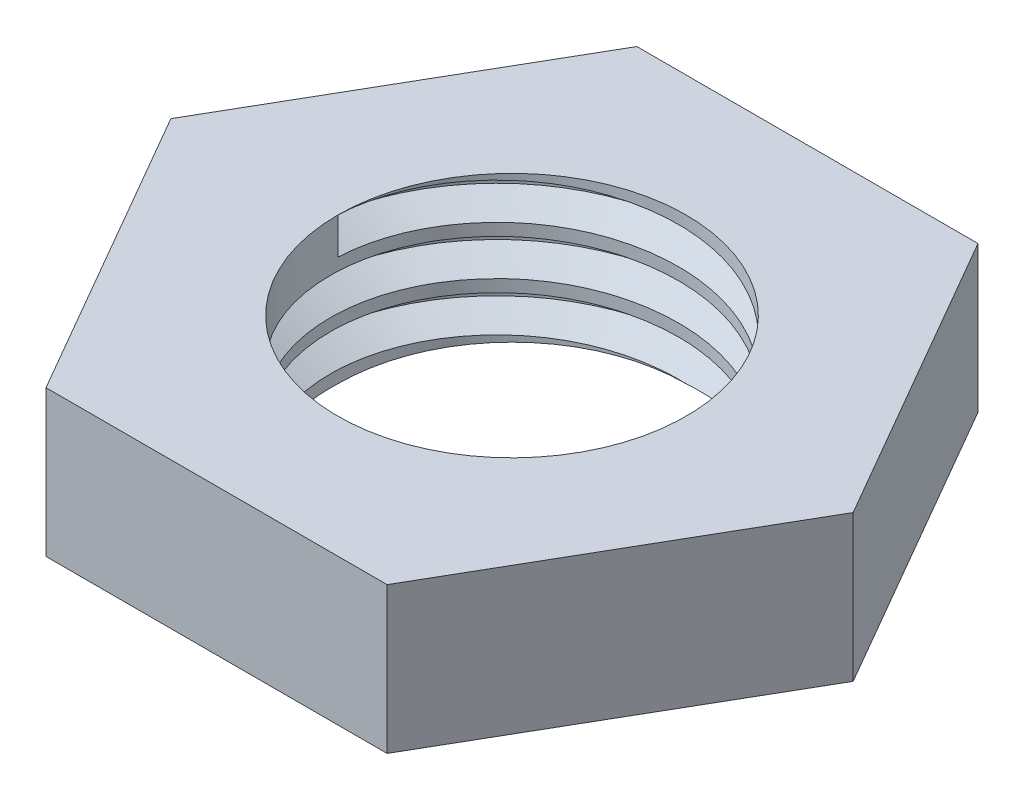
SolidWorks part; units mm, degrees
ref_plane "Front Plane" through (0, 0, 0) normal (0, 0, 1) x (1, 0, 0)
ref_plane "Top Plane" through (0, 0, 0) normal (0, 1, 0) x (1, 0, 0)
ref_plane "Right Plane" through (0, 0, 0) normal (1, 0, 0) x (0, 0, -1)
sketch "Sketch1" plane through (0, 0, 0) normal (0, 1, 0) x (1, 0, 0)
  line L1 (7, 0) -> (3.5, 6.0622)
  line L2 (3.5, 6.0622) -> (-3.5, 6.0622)
  line L3 (-3.5, 6.0622) -> (-7, 0)
  line L4 (-7, 0) -> (-3.5, -6.0622)
  line L5 (-3.5, -6.0622) -> (3.5, -6.0622)
  line L6 (3.5, -6.0622) -> (7, 0)
  circle A0 centre (0, 0) radius 6.0622 construction
  circle A1 centre (0, 0) radius 3.575
  dimension "D2" = 7.15
  dimension "D1" = 7
extrude "Boss-Extrude1" add sketch "Sketch1" along normal blind 3
thread "Thread1" pitch 1 method cut profile "Thread Profile1" start angle 0, offset 0, length 0, pitch 1, diameter 7.15
ref_plane "Plane1" through (-3.575, 3, 0) normal (0, 0, 1) x (-1, 0, 0)
sketch "Thread Profile1" plane through (-3.575, 3, 0) normal (0, 0, 1) x (-1, 0, 0)
  line L0 (0, 0) -> (0, 1) construction
  line L1 (0, 0) -> (0.5413, 0.3125)
  line L2 (0.5413, 0.3125) -> (0.5413, 0.4375)
  line L3 (0.5413, 0.4375) -> (0, 0.75)
  line L4 (0.5413, 0.375) -> (0, 0.375) construction
  line L11 (0, 0) -> (0, 0.75)
  point P2 (0, 0)
  dimension "Pitch" = 1
  dimension "Profile_Angle" = 60
  dimension "Profile_Land" = 0.125
  dimension "Profile_Height" = 0.5413
equation "\"D2@Sketch1\"=7+0.15"
